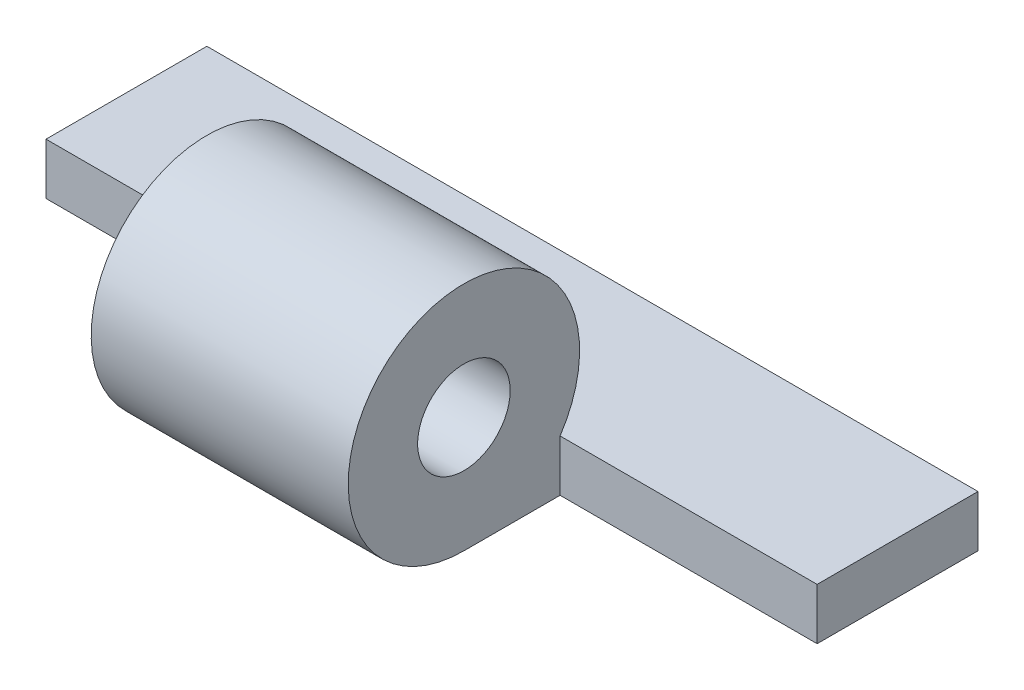
SolidWorks part; units mm, degrees
ref_plane "Ebene vorne" through (0, 0, 0) normal (0, 0, 1) x (1, 0, 0)
ref_plane "Ebene oben" through (0, 0, 0) normal (0, 1, 0) x (1, 0, 0)
ref_plane "Ebene rechts" through (0, 0, 0) normal (1, 0, 0) x (0, 0, -1)
sketch "Skizze2" plane through (0, 0, 0) normal (0, 1, 0) x (1, 0, 0)
  line L1 (-7.5, 2.5) -> (7.5, 2.5)
  line L2 (-7.5, 2.5) -> (-7.5, -2.5)
  line L3 (-7.5, -2.5) -> (7.5, -2.5)
  line L4 (7.5, 2.5) -> (7.5, -2.5)
  line L5 (-7.5, 2.5) -> (7.5, -2.5) construction
  line L6 (-7.5, -2.5) -> (7.5, 2.5) construction
  point P0 (0, 0)
  dimension "D1" = 15
  dimension "D2" = 5
extrude "Aufsatz-Linear austragen1" add sketch "Skizze2" along normal blind 1
sketch "Skizze3" plane through (7.5, 0, 0) normal (1, 0, 0) x (0, 0, -1)
  circle A0 centre (-2.5, 2.25) radius 2.25
  circle A1 centre (-2.5, 2.25) radius 0.9
  dimension "D1" = 1.8
  dimension "D2" = 4.5
extrude "Aufsatz-Linear austragen2" add sketch "Skizze3" against normal up to surface (15 mm away) up to face at (-7.5, 0.5, 0)
ref_plane "Tangential Ebene" through (0, 0, 0.25) normal (0, 0, -1) x (-1, 0, 0)
sketch "Skizze5" plane through (7.5, 0, 0) normal (1, 0, 0) x (0, 0, -1)
  line L0 (-0.6292, 1) -> (-0.6292, 0)
  line L1 (-0.6292, 0) -> (-2.5, 0)
  line L3 (2.5, 1) -> (-0.6292, 1)
  line L4 (-2.5, 0) -> (2.5, 0)
  line L5 (2.5, 0) -> (2.5, 1)
  line L6 (2.5, 1) -> (-0.6292, 1) construction
  line L7 (-2.5, 0) -> (2.5, 0) construction
  line L8 (2.5, 0) -> (2.5, 1) construction
  arc A1 (-0.6292, 1) -> (-2.5, 0) centre (-2.5, 2.25) ccw
  arc A2 (-0.6292, 1) -> (-2.5, 0) centre (-2.5, 2.25) ccw
  dimension "D1" = 0
extrude "Schnitt-Linear austragen1" cut sketch "Skizze5" against normal blind 5
pattern_linear "Lineares Muster1" count 2 spacing 10 along (-1, 0, 0) of "Schnitt-Linear austragen1"
